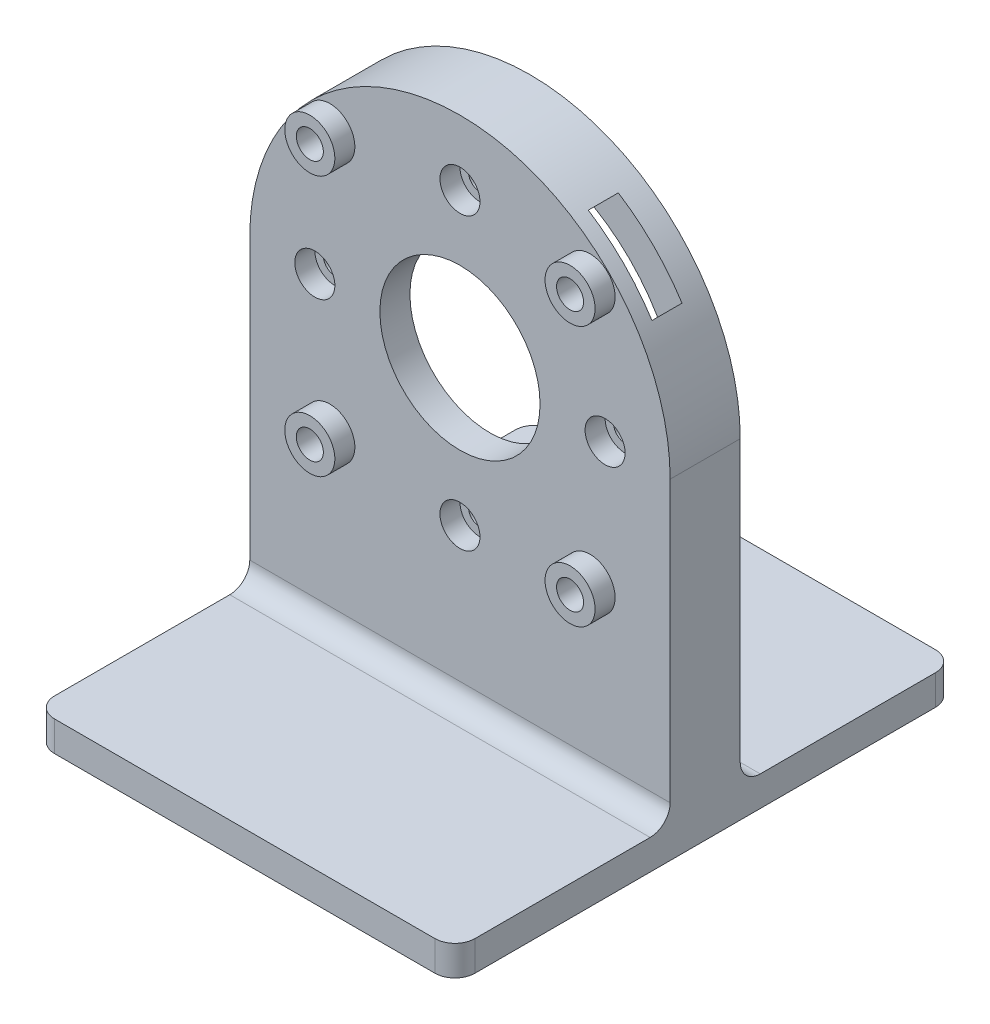
SolidWorks part; units mm, degrees
ref_plane "Front Plane" through (0, 0, 0) normal (0, 0, 1) x (1, 0, 0)
ref_plane "Top Plane" through (0, 0, 0) normal (0, 1, 0) x (1, 0, 0)
ref_plane "Right Plane" through (0, 0, 0) normal (1, 0, 0) x (0, 0, -1)
sketch "Sketch1" plane through (0, 0, 0) normal (0, 0, 1) x (1, 0, 0)
  line L1 (-21, 0) -> (21, 0)
  line L2 (-21, 0) -> (-21, 30)
  line L4 (21, 0) -> (21, 30)
  arc A0 (21, 30) -> (-21, 30) centre (0, 30) ccw
  circle A1 centre (0, 30) radius 8
  point P4 (0, 0)
  dimension "D1" = 21
  dimension "D3" = 16
  dimension "D2" = 30
extrude "Boss-Extrude1" add sketch "Sketch1" along normal blind 7
sketch "Sketch2" plane through (0, 0, 0) normal (0, 0, -1) x (-1, 0, 0)
  circle A0 centre (0, 30) radius 17.65
  dimension "D1" = 35.3
extrude "Cut-Extrude1" cut sketch "Sketch2" against normal blind 4
sketch "Sketch4" plane through (0, 0, 7) normal (0, 0, 1) x (1, 0, 0)
  circle A0 centre (0, 30) radius 14.5 construction
  circle A1 centre (0, 44.5) radius 1.15
  dimension "D1" = 29
  dimension "D2" = 2.3
extrude "Cut-Extrude2" cut sketch "Sketch4" against normal up to next
sketch "Sketch5" plane through (0, 0, 7) normal (0, 0, 1) x (1, 0, 0)
  circle A0 centre (0, 44.5) radius 2
  dimension "D1" = 4
extrude "Cut-Extrude3" cut sketch "Sketch5" against normal blind 2
sketch "Sketch6" plane through (0, 0, 7) normal (0, 0, 1) x (1, 0, 0)
  line L0 (0, 30) -> (-13, 43) construction
  line L1 (-21, 0) -> (21, 0) construction
  line L2 (-13, 43) -> (-13, 17) construction
  circle A0 centre (0, 30) radius 18.3848 construction
  circle A1 centre (-13, 43) radius 2.5
  circle A2 centre (-13, 43) radius 1.35
  dimension "D1" = 45
  dimension "D3" = 5
  dimension "D4" = 2.7
  dimension "D2" = 26
extrude "Boss-Extrude2" add sketch "Sketch6" along normal blind 2
extrude "Cut-Extrude4" cut sketch "Sketch6<2>" against normal blind 2 contours A2 region at (-13, 43, 7)
sketch "Sketch6<2>" plane through (0, 0, 7) normal (0, 0, 1) x (1, 0, 0) same geometry as "Sketch6"
pattern_circular "CirPattern3" count 4 over 360 about axis through (0, 30, 7) along (0, 0, -1) of "Cut-Extrude2", "Cut-Extrude3", "Boss-Extrude2", "Cut-Extrude4" reverse direction yes
sketch "Sketch7" plane through (0, 0, 0) normal (0, -1, 0) x (1, 0, 0)
  line L0 (-21, 7) -> (-21, 0) construction
  line L1 (-21, -21.5) -> (21, -21.5)
  line L2 (-21, -21.5) -> (-21, 28.5)
  line L3 (-21, 28.5) -> (21, 28.5)
  line L4 (21, -21.5) -> (21, 28.5)
  line L6 (21, 7) -> (21, 0) construction
  point P8 (21, 3.5)
  point P9 (21, 3.5)
  dimension "D1" = 50
extrude "Boss-Extrude3" add sketch "Sketch7" along normal blind 3
fillet "Fillet1" radius 2 6 edges at (0, 0, 7) (0, 0, 0) (21, -1.5, -21.5) (-21, -1.5, -21.5) (21, -1.5, 28.5) (-21, -1.5, 28.5)
ref_plane "Plane1" through (22.25, 22.25, 0) normal (0.7071, 0.7071, 0) x (0.7071, -0.7071, 0)
sketch "Sketch8" plane through (22.25, 22.25, 0) normal (0.7071, 0.7071, 0) x (0.7071, -0.7071, 0)
  line L0 (-21.2132, -7) -> (-21.2132, 0) construction
  line L1 (-25.7132, -2.5) -> (-16.7132, -2.5)
  line L2 (-25.7132, -2.5) -> (-25.7132, -5.5)
  line L3 (-25.7132, -5.5) -> (-16.7132, -5.5)
  line L4 (-16.7132, -2.5) -> (-16.7132, -5.5)
  line L5 (-42.2132, -7) -> (-6.364, -7) construction
  line L7 (-30.3163, -4) -> (-32.6163, -4) construction
  point P4 (-21.2132, -2.5)
  point P9 (-25.7132, -4)
  dimension "D1" = 1.5
  dimension "D2" = 9
extrude "Cut-Extrude5" cut sketch "Sketch8" along normal up to next
